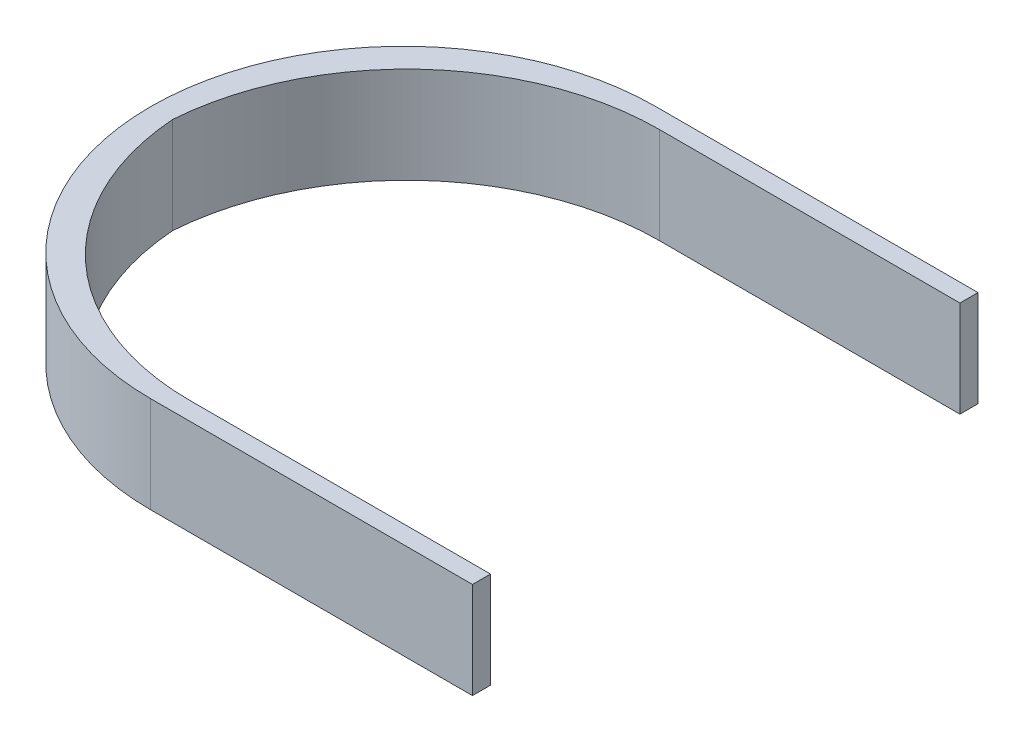
SolidWorks part; units mm, degrees
ref_plane "Alzado" through (0, 0, 0) normal (0, 0, 1) x (1, 0, 0)
ref_plane "Planta" through (0, 0, 0) normal (0, 1, 0) x (1, 0, 0)
ref_plane "Vista lateral" through (0, 0, 0) normal (1, 0, 0) x (0, 0, -1)
sketch "Croquis3" plane through (0, 0, 0) normal (0, 1, 0) x (1, 0, 0)
  line L0 (13.8814, 1.5) -> (13.8814, 40.5)
  line L1 (0, 0) -> (50, 0)
  line L2 (0, 0) -> (0, 42)
  line L3 (0, 42) -> (50, 42)
  line L4 (50, 0) -> (50, 42)
  line L6 (31.0404, 1.5) -> (13.8814, 1.5)
  line L7 (1.7857, 40.5) -> (48.2143, 40.5)
  line L8 (1.7857, 40.5) -> (1.7857, 1.5)
  line L9 (1.7857, 1.5) -> (48.2143, 1.5)
  line L10 (48.2143, 40.5) -> (48.2143, 1.5)
  line L11 (31.0404, 1.5) -> (31.0404, 40.5)
  line L12 (13.8814, 40.5) -> (31.0404, 40.5)
  point P5 (25, 21)
  dimension "D1" = 42
  dimension "D2" = 50
  dimension "D3" = 39
extrude "Saliente-Extruir7" add sketch "Croquis3" along normal blind 8 contours L2 L3 L4 L1
extrude "Cortar-Extruir2" cut sketch "Croquis3<13>" against normal blind 8 and the other way blind 8 contours L8 L9 L10 L7
sketch "Croquis3<13>" plane through (0, 0, 0) normal (0, 1, 0) x (1, 0, 0) same geometry as "Croquis3"
fillet "Redondeo3" radius 21 4 edges at (0, 4, 0) (1.7857, 4, -1.5) (1.7857, 4, -40.5) (0, 4, -42)
sketch "Croquis7" plane through (0, 8, 0) normal (0, 1, 0) x (1, 0, 0)
  line L1 (47.7497, 43.2268) -> (47.7497, -2.7885)
  line L2 (51.1433, -2.7885) -> (51.1433, 43.2268)
  line L3 (51.1433, 43.2268) -> (47.7497, 43.2268)
  line L4 (47.7497, -2.7885) -> (51.1433, -2.7885)
extrude "Cortar-Extruir3" cut sketch "Croquis7" against normal blind 8
